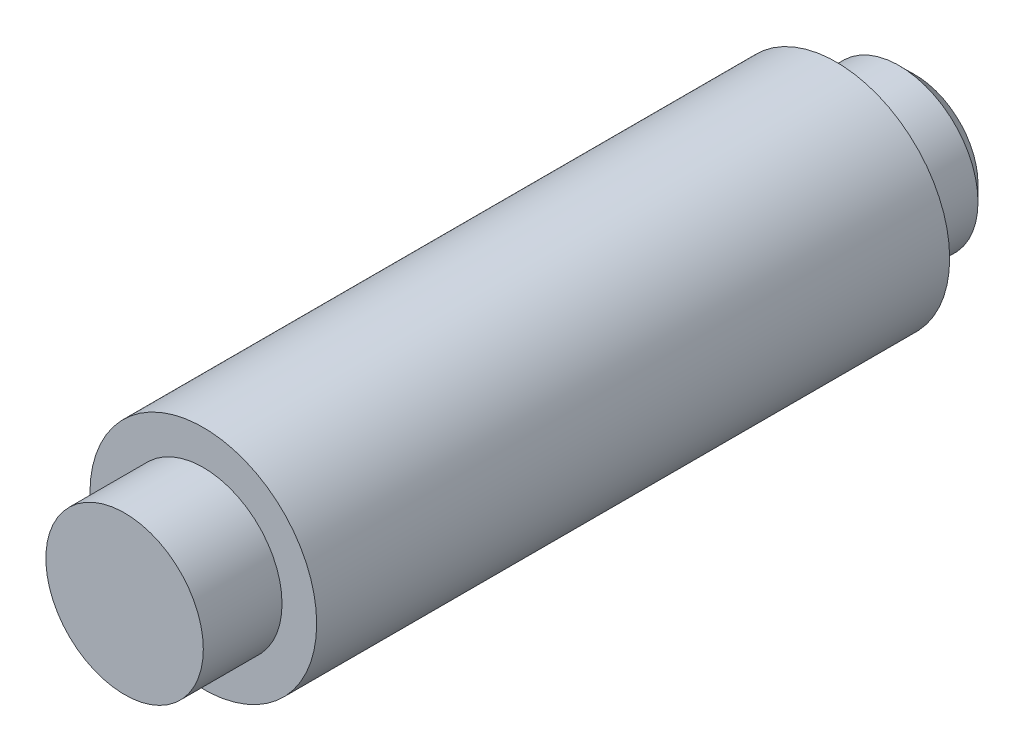
SolidWorks part; units mm, degrees
ref_plane "Front Plane" through (0, 0, 0) normal (0, 0, 1) x (1, 0, 0)
ref_plane "Top Plane" through (0, 0, 0) normal (0, 1, 0) x (1, 0, 0)
ref_plane "Right Plane" through (0, 0, 0) normal (1, 0, 0) x (0, 0, -1)
sketch "Sketch2" plane through (0, 0, 0) normal (0, 0, 1) x (1, 0, 0)
  circle A0 centre (0, 0) radius 1.25
  dimension "D1" = 2.5
sketch "Sketch3" plane through (0, 0, 0) normal (0, 0, 1) x (1, 0, 0)
  line L5 (-3.6, 3.6) -> (3.6, 3.6) construction
  line L6 (-3.6, 3.6) -> (-3.6, -3.6) construction
  line L7 (-3.6, -3.6) -> (3.6, -3.6) construction
  line L8 (3.6, 3.6) -> (3.6, -3.6) construction
  circle A0 centre (0, 0) radius 3.6
  point P4 (0, 3.6)
  point P6 (-3.6, 0)
  dimension "D1" = 7.2
extrude "Boss-Extrude1" add sketch "Sketch3" along normal blind 20.1
sketch "Sketch4" plane through (0, 0, 0) normal (0, 0, 1) x (1, 0, 0)
  circle A0 centre (0, 0) radius 2.5
  dimension "D1" = 5
extrude "Boss-Extrude2" add sketch "Sketch4" against normal blind 2.5
sketch "Sketch5" plane through (0, 0, 20.1) normal (0, 0, 1) x (1, 0, 0)
  circle A0 centre (0, 0) radius 2.5
  dimension "D1" = 5
extrude "Boss-Extrude3" add sketch "Sketch5" along normal blind 2.5
chamfer "Chamfer1" distance 0.5 angle 45 1 edges at (2.5, 0, -2.5)
equation "\"length\"=20.1"
equation "\"D1@Boss-Extrude1\"=\"length\""
